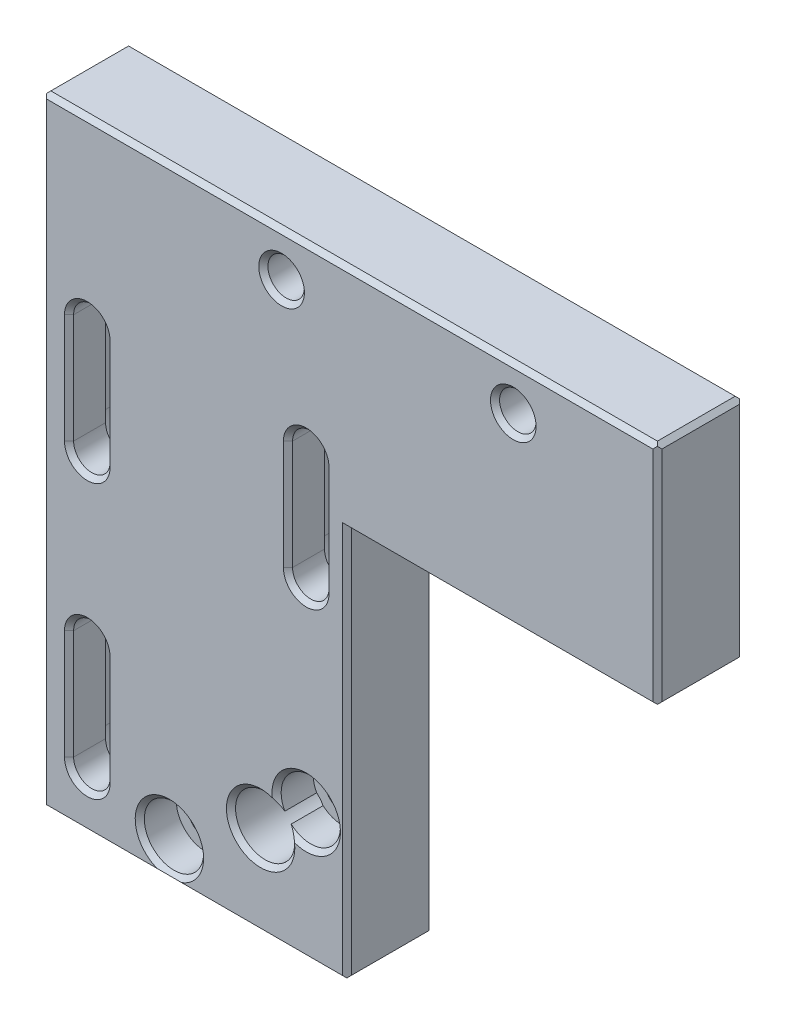
SolidWorks part; units mm, degrees
ref_plane "Front Plane" through (0, 0, 0) normal (0, 0, 1) x (1, 0, 0)
ref_plane "Top Plane" through (0, 0, 0) normal (0, 1, 0) x (1, 0, 0)
ref_plane "Right Plane" through (0, 0, 0) normal (1, 0, 0) x (0, 0, -1)
sketch "Sketch1" plane through (0, 0, 0) normal (0, 0, 1) x (1, 0, 0)
  line L0 (0, 0) -> (24.45, 0)
  line L1 (30, -16) -> (30, 43) construction
  line L3 (24.45, 43) -> (24.45, 0)
  line L4 (24.45, 0) -> (24.6859, 0.0472)
  line L6 (24.45, 43) -> (58.5, 43)
  line L8 (0, 68) -> (58.5, 68)
  line L9 (58.5, 43) -> (58.5, 68)
  line L10 (0, 0) -> (-9, 0)
  line L12 (0, 68) -> (-9, 68)
  line L13 (-9, 0) -> (-9, 68)
  circle A0 centre (5, 4) radius 2
  circle A1 centre (20, 14) radius 2
  circle A2 centre (15, 10) radius 3.25
  circle A3 centre (5, 4) radius 3.25
  circle A4 centre (30, -16) radius 6.55
  circle A5 centre (20, 14) radius 3.25
  circle A6 centre (17.3, 63.2375) radius 2
  circle A7 centre (42.7, 63.2375) radius 2
  dimension "D3" = 4
  dimension "D7" = 4
  dimension "D10" = 6.5
  dimension "D13" = 13.1
  dimension "D19" = 6.5
  dimension "D20" = 6.5
  dimension "D23" = 4
  dimension "D24" = 4
  dimension "D1" = 24.45
  dimension "D2" = 4
  dimension "D4" = 5
  dimension "D5" = 20
  dimension "D6" = 14
  dimension "D8" = 10
  dimension "D9" = 15
  dimension "D11" = 30
  dimension "D12" = 16
  dimension "D14" = 43
  dimension "D15" = 58.5
  dimension "D16" = 67.5
  dimension "D17" = 9
  dimension "D18" = 68
  dimension "D21" = 12.7
  dimension "D22" = 12.7
  dimension "D25" = 4.7625
extrude "Boss-Extrude1" add sketch "Sketch1" along normal blind 9.525 contours L13 L10 L0 L3 L6 L9 L8 L12 A2 A1 A0 region at (16.9253, 40.6709, 0)
extrude "Boss-Extrude3" add sketch "Sketch1<4>" along normal blind 5.525 contours A2 A5 A1 | A3 A0 region at (17.6096, 12.0877, 0) region at (1.8419, 4, 0)
sketch "Sketch1<4>" plane through (0, 0, 0) normal (0, 0, 1) x (1, 0, 0) same geometry as "Sketch1"
sketch "Sketch3" plane through (0, 0, 9.525) normal (0, 0, 1) x (1, 0, 0)
  line L0 (-2, 18) -> (-2, 6)
  line L1 (-9, 0) -> (-9, 68) construction
  line L2 (24.45, 0) -> (-9, 0) construction
  line L3 (-6, 18) -> (-6, 6)
  line L4 (-6, 48) -> (-6, 36)
  line L5 (-2, 48) -> (-2, 36)
  line L6 (18, 48) -> (18, 36)
  line L7 (22, 48) -> (22, 36)
  arc A0 (-2, 18) -> (-6, 18) centre (-4, 18) ccw
  arc A1 (-2, 48) -> (-6, 48) centre (-4, 48) ccw
  arc A2 (22, 48) -> (18, 48) centre (20, 48) ccw
  arc A7 (-6, 6) -> (-2, 6) centre (-4, 6) ccw
  arc A8 (-6, 36) -> (-2, 36) centre (-4, 36) ccw
  arc A11 (18, 36) -> (22, 36) centre (20, 36) ccw
  dimension "D3" = 4
  dimension "D4" = 4
  dimension "D5" = 4
  dimension "D6" = 5
  dimension "D7" = 6
  dimension "D8" = 12
  dimension "D11" = 4
  dimension "D12" = 4
  dimension "D13" = 4
  dimension "D1" = 24
  dimension "D2" = 30
  dimension "D9" = 12
  dimension "D10" = 12
  dimension "D14" = 12
  dimension "D15" = 12
  dimension "D16" = 12
  dimension "D17" = 12
  dimension "D18" = 12
  dimension "D19" = 12
extrude "Cut-Extrude1" cut sketch "Sketch3" against normal through all
sketch "Sketch4" plane through (0, 0, 0) normal (0, 0, -1) x (-1, 0, 0)
  line L4 (-16.75, 36) -> (-16.75, 48)
  line L5 (-23.25, 48) -> (-23.25, 36)
  line L8 (0.75, 48) -> (0.75, 36)
  line L9 (7.25, 36) -> (7.25, 48)
  line L12 (7.25, 6) -> (7.25, 18)
  line L13 (0.75, 17.9953) -> (0.75, 5.9953)
  arc A0 (2, 6) -> (6, 6) centre (4, 6) ccw construction
  arc A1 (6, 18) -> (2, 18) centre (4, 18) ccw construction
  arc A2 (2, 36) -> (6, 36) centre (4, 36) ccw construction
  arc A3 (6, 48) -> (2, 48) centre (4, 48) ccw construction
  arc A4 (-23.25, 36) -> (-16.75, 36) centre (-20, 36) ccw
  arc A5 (-16.75, 48) -> (-23.25, 48) centre (-20, 48) ccw
  arc A6 (-22, 36) -> (-18, 36) centre (-20, 36) ccw construction
  arc A7 (-18, 48) -> (-22, 48) centre (-20, 48) ccw construction
  arc A8 (0.75, 36) -> (7.25, 36) centre (4, 36) ccw
  arc A9 (7.25, 48) -> (0.75, 48) centre (4, 48) ccw
  arc A12 (0.75, 5.9953) -> (7.25, 6) centre (4, 6) ccw
  arc A13 (7.25, 18) -> (0.75, 17.9953) centre (4, 18) ccw
  dimension "D4" = 3.25
  dimension "D1" = 3.25
  dimension "D6" = 3.25
  dimension "D7" = 3.25
  dimension "D11" = 3.25
  dimension "D12" = 3.25
  dimension "D2" = 12
  dimension "D3" = 12
  dimension "D5" = 6.5
  dimension "D8" = 12
  dimension "D9" = 12
  dimension "D10" = 6.5
  dimension "D13" = 12
  dimension "D14" = 12
  dimension "D15" = 6.5
extrude "Cut-Extrude2" cut sketch "Sketch4" against normal blind 5.525
chamfer "Chamfer1" distance 0.5 angle 45 1 edges at (-9, 68, 4.7625)
chamfer "Chamfer2" distance 0.5 angle 45 4 edges at (-9, 0, 4.7625) (24.45, 0, 4.7625) (58.5, 43, 4.7625) (58.5, 68, 4.7625)
chamfer "Chamfer3" distance 0.5 angle 45 12 edges at (24.75, 68, 0) (58.5, 55.5, 0) (41.225, 43, 0) (24.45, 21.75, 0) (24.75, 68, 9.525) (58.5, 55.5, 9.525) (41.225, 43, 9.525) (24.45, 21.75, 9.525) (7.725, 0, 0) (7.725, 0, 9.525) (-9, 34, 0) (-9, 34, 9.525)
chamfer "Chamfer4" distance 0.5 angle 45 17 edges at (44.7, 63.2375, 9.525) (19.3, 63.2375, 9.525) (20, 34, 9.525) (22, 42, 9.525) (20, 50, 9.525) (18, 42, 9.525) (-4, 34, 9.525) (-2, 42, 9.525) (-4, 50, 9.525) (-6, 42, 9.525) (-6, 12, 9.525) (-4, 4, 9.525) (-2, 12, 9.525) (-4, 20, 9.525) (8.25, 4, 9.525) (22.5378, 16.0303, 9.525) (12.4622, 7.9697, 9.525)
sketch "Sketch5" plane through (0, 0, 0) normal (0, 0, -1) x (-1, 0, 0)
  circle A1 centre (-42.7, 63.2375) radius 3.25
  circle A2 centre (-17.3, 63.2375) radius 3.25
  dimension "D1" = 6.5
  dimension "D2" = 6.5
extrude "Cut-Extrude3" cut sketch "Sketch5" against normal blind 5.525
chamfer "Chamfer5" distance 0.5 angle 45 17 edges at (22, 14, 0) (18.25, 10, 0) (7, 4, 0) (-0.75, 11.9953, 0) (-4.0023, 2.75, 0) (-7.25, 12, 0) (-3.9977, 21.25, 0) (-4, 32.75, 0) (-7.25, 42, 0) (-4, 51.25, 0) (-0.75, 42, 0) (20, 32.75, 0) (23.25, 42, 0) (16.75, 42, 0) (20, 51.25, 0) (39.45, 63.2375, 0) (14.05, 63.2375, 0)
